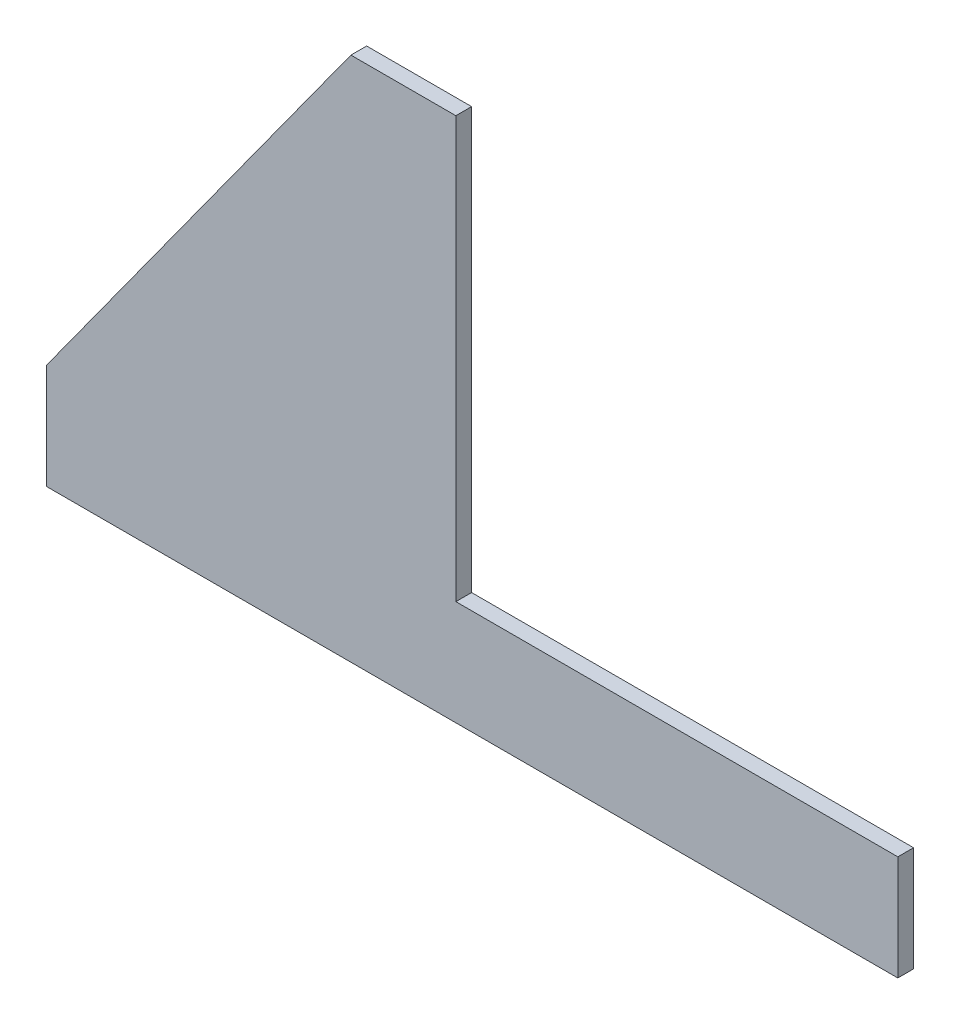
SolidWorks part; units mm, degrees
ref_plane "Alzado" through (0, 0, 0) normal (0, 0, 1) x (1, 0, 0)
ref_plane "Planta" through (0, 0, 0) normal (0, 1, 0) x (1, 0, 0)
ref_plane "Vista lateral" through (0, 0, 0) normal (1, 0, 0) x (0, 0, -1)
sketch "Croquis1" plane through (0, 0, 0) normal (0, 0, 1) x (1, 0, 0)
  line L0 (-15.5, 50) -> (405.6, 50)
  line L1 (-405.6, -50) -> (405.6, -50)
  line L2 (-405.6, -50) -> (-405.6, 50)
  line L3 (-405.6, 50) -> (-115.5, 451)
  line L4 (405.6, -50) -> (405.6, 50)
  line L5 (-405.6, -50) -> (405.6, 50) construction
  line L6 (-405.6, 50) -> (405.6, -50) construction
  line L7 (-115.5, 451) -> (-15.5, 451)
  line L8 (-15.5, 451) -> (-15.5, 50)
  line L9 (-405.6, 50) -> (-15.5, 50) construction
  point P0 (0, 0)
  dimension "D1" = 811.2
  dimension "D2" = 100
  dimension "D3" = 100
  dimension "D4" = 390.1
  dimension "D5" = 401
extrude "Saliente-Extruir1" add sketch "Croquis1" along normal blind 15
sketch "Croquis2" plane through (0, 0, 15) normal (0, 0, 1) x (1, 0, 0)
  line L0 (0, -50) -> (0, 50) construction
  line L3 (-405.6, 0) -> (405.6, 0) construction
  line L4 (-405.6, 50) -> (-405.6, -50) construction
  line L5 (405.6, -50) -> (405.6, 50) construction
  line L6 (-405.6, -50) -> (405.6, -50) construction
  line L7 (405.6, 50) -> (-15.5, 50) construction
sketch "Croquis3" plane through (0, 50, 0) normal (0, 1, 0) x (1, 0, 0)
  line L0 (0, -15) -> (0, 0) construction
